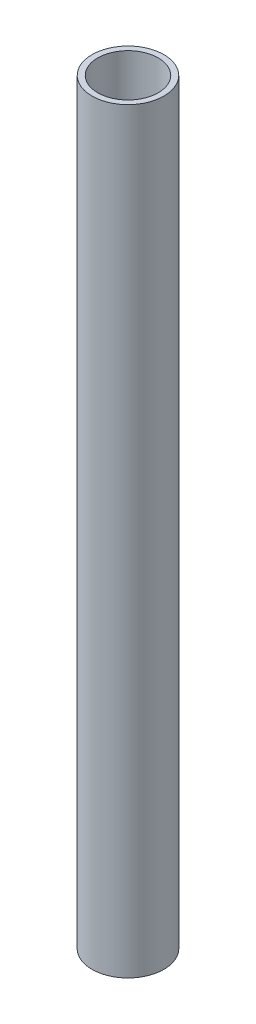
SolidWorks part; units mm, degrees
note: '?' marks a value the reader was unsure of.
ref_plane "Front Plane" through (0, 0, 0) normal (0, 0, 1) x (1, 0, 0)
ref_plane "Top Plane" through (0, 0, 0) normal (0, 1, 0) x (1, 0, 0)
ref_plane "Right Plane" through (0, 0, 0) normal (1, 0, 0) x (0, 0, -1)
sketch "Sketch1" plane through (0, 0, 0) normal (0, 1, 0) x (1, 0, 0)
  circle A0 centre (0, 0) radius 8
  circle A1 centre (0, 0) radius 9.5
  dimension "D1" = 16
  dimension "D2" = 19
extrude "Boss-Extrude1" add sketch "Sketch1" along normal blind 200
ref_axis "Axis1" through (0, 200, 0) along (0, -1, 0)?
thread "Thread1" [suppressed] pitch 6.35 start angle 0, offset 3, length 13, pitch 6.35, diameter 20
ref_plane "Plane1" through (-10, 203, 0) normal (0, 0, 1) x (-1, 0, 0)
sketch "Thread Profile1" plane through (-10, 203, 0) normal (0, 0, 1) x (-1, 0, 0)
  line L0 (0, 0) -> (0, 6.35) construction
  line L11 (0, 0) -> (0, 5.5562)
  line L12 (0, 5.5562) -> (-3.437, 3.5719)
  line L13 (-3.437, 3.5719) -> (-3.437, 1.9844)
  line L15 (-3.437, 1.9844) -> (0, 0)
  line L17 (-3.437, 2.7781) -> (0, 2.7781) construction
  point P2 (0, 0)
  dimension "Pitch" = 6.35
  dimension "Profile_Angle" = 60
  dimension "Profile_Land" = 1.5875
  dimension "Profile_Height" = 3.437
fillet "Fillet1" [suppressed] radius 1
fillet "Fillet2" [suppressed] radius 1
sketch "Sketch23" [suppressed] plane through (0, 190, 0) normal (0, 1, 0) x (1, 0, 0)
  circle A0 centre (0, 0) radius 17.5
  circle A1 centre (0, 0) radius 10
  dimension "D1" = 20
  dimension "D2" = 35
